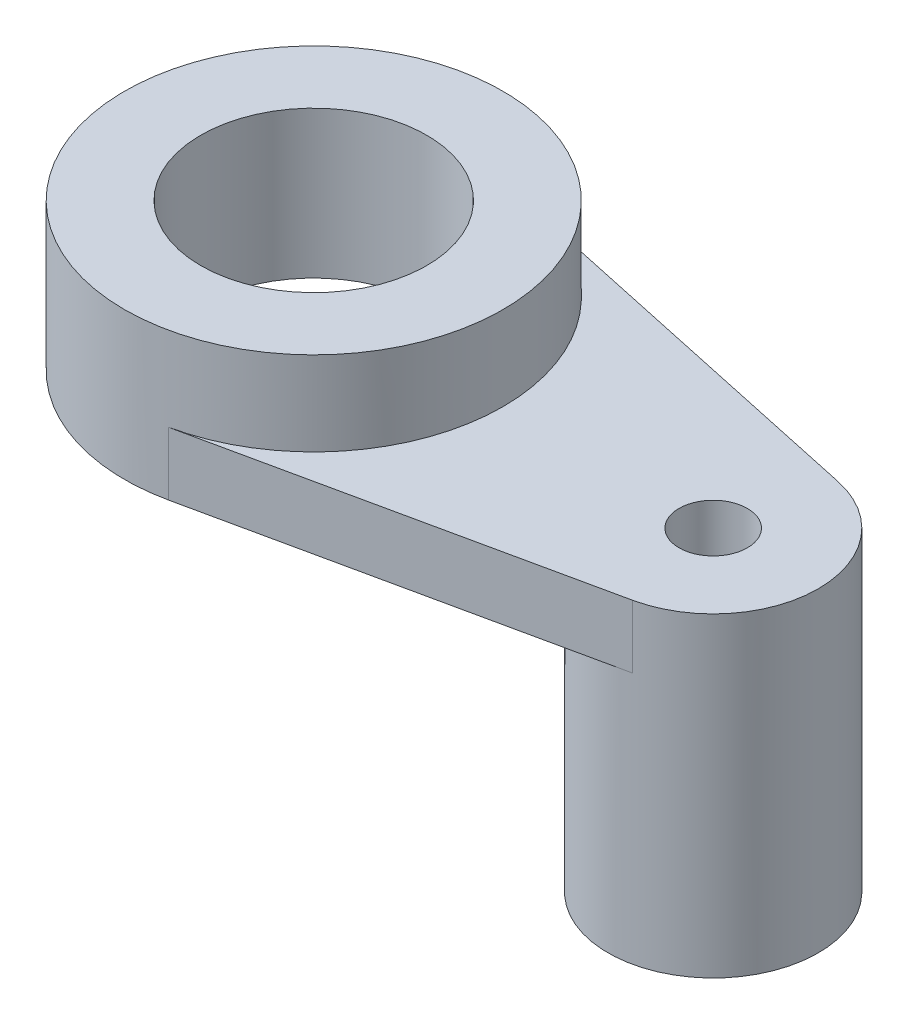
SolidWorks part; units mm, degrees
material "1060 Alloy"
ref_plane "Front Plane" through (0, 0, 0) normal (0, 0, 1) x (1, 0, 0)
ref_plane "Top Plane" through (0, 0, 0) normal (0, 1, 0) x (1, 0, 0)
ref_plane "Right Plane" through (0, 0, 0) normal (1, 0, 0) x (0, 0, -1)
sketch "Sketch1" plane through (0, 0, 0) normal (0, 1, 0) x (1, 0, 0)
  line L0 (0, -1361.333) -> (0, 66705.3177) construction
  line L1 (-1361.333, 0) -> (66705.3177, 0) construction
  line L2 (40.1053, 9.7759) -> (3.7895, 17.5966)
  line L3 (40.1053, -9.7759) -> (3.7895, -17.5966)
  circle A0 centre (0, 0) radius 18
  circle A1 centre (0, 0) radius 10.75
  arc A3 (40.1053, -9.7759) -> (40.1053, 9.7759) centre (38, 0) ccw
  dimension "D1" = 36
  dimension "D2" = 21.5
  dimension "D4" = 38
extrude "Boss-Extrude1" add sketch "Sketch1" along normal blind 14 contours A0 A1 region at (13.6077, 0, -10.9892)
sketch "Sketch2" plane through (0, 0, 0) normal (0, 1, 0) x (1, 0, 0)
sketch "Sketch3" plane through (0, 0, 0) normal (0, 1, 0) x (1, 0, 0)
extrude "Boss-Extrude2" add sketch "Sketch1<4>" along normal blind 6 contours L3 A3 L2 A0 region at (29.1776, 0, 0)
sketch "Sketch1<4>" plane through (0, 0, 0) normal (0, 1, 0) x (1, 0, 0) same geometry as "Sketch1"
sketch "Sketch6" plane through (0, 0, 0) normal (0, -1, 0) x (1, 0, 0)
  circle A0 centre (38, 0) radius 10
  arc A1 (40.1053, -9.7759) -> (40.1053, 9.7759) centre (38, 0) ccw construction
  dimension "D1" = 20
extrude "Boss-Extrude3" add sketch "Sketch6" along normal blind 24
sketch "Sketch7" plane through (0, -24, 0) normal (0, -1, 0) x (1, 0, 0)
  circle A0 centre (38, 0) radius 3.25
  circle A1 centre (38, 0) radius 10 construction
  dimension "D1" = 6.5
extrude "Cut-Extrude1" cut sketch "Sketch7" against normal through all
